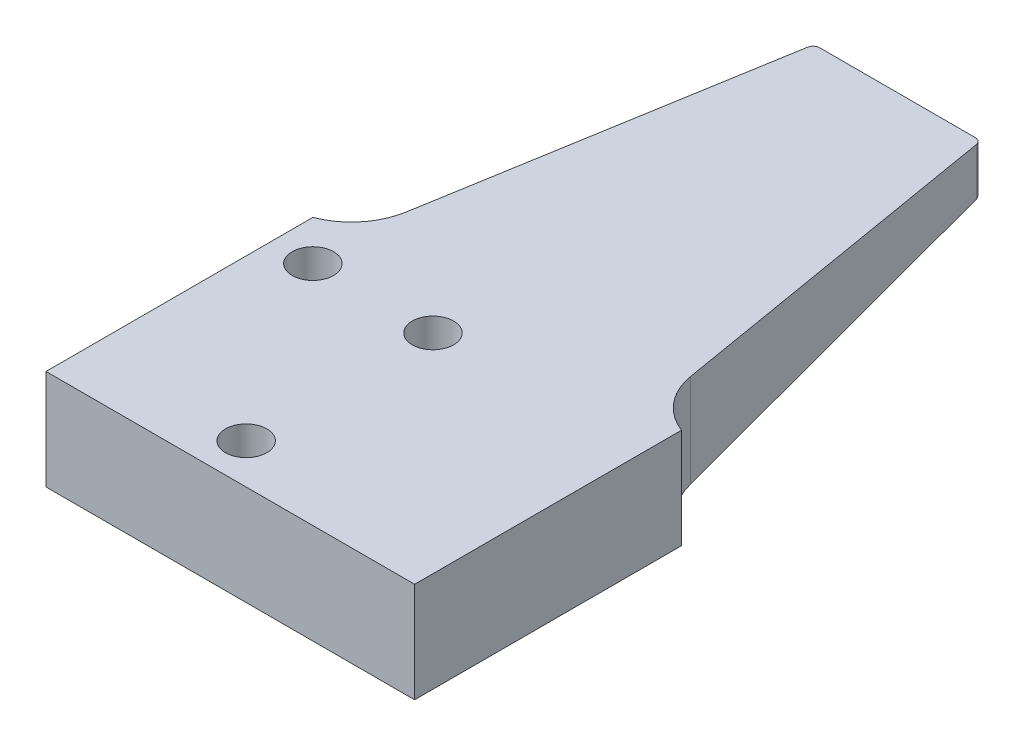
SolidWorks part; units mm, degrees
material "ABS"
ref_plane "Front Plane" through (0, 0, 0) normal (0, 0, 1) x (1, 0, 0)
ref_plane "Top Plane" through (0, 0, 0) normal (0, 1, 0) x (1, 0, 0)
ref_plane "Right Plane" through (0, 0, 0) normal (1, 0, 0) x (0, 0, -1)
sketch "Sketch1" plane through (0, 0, 0) normal (0, 1, 0) x (1, 0, 0)
  line L1 (0, 0) -> (55.25, 0)
  line L2 (0, 0) -> (0, 100)
  line L3 (0, 100) -> (55.25, 100)
  line L4 (55.25, 0) -> (55.25, 100)
  circle A6 centre (24, 6) radius 1.6
  circle A7 centre (6, 34) radius 1.6
  circle A8 centre (24, 34) radius 1.6
  dimension "D1" = 100
  dimension "D2" = 55.25
extrude "Boss-Extrude1" add sketch "Sketch1" along normal blind 15
sketch "Sketch2" plane through (0, 15, 0) normal (0, 1, 0) x (1, 0, 0)
  circle A0 centre (24, 34) radius 3.1
  circle A1 centre (24, 6) radius 3.1
  circle A4 centre (24, 34) radius 1.6 construction
  circle A5 centre (24, 6) radius 1.6 construction
  circle A6 centre (6, 34) radius 3.1
  circle A7 centre (6, 34) radius 1.6 construction
  dimension "D2" = 6.2
  dimension "D3" = 6.2
  dimension "D1" = 6.2
extrude "Cut-Extrude1" cut sketch "Sketch2" against normal blind 7.5
sketch "Sketch5" plane through (55.25, 0, 0) normal (1, 0, 0) x (0, 0, -1)
  line L0 (40, 0) -> (100, 8)
  line L1 (0, 0) -> (100, 0) construction
  line L2 (100, 8) -> (100, 0)
  line L3 (100, 0) -> (40, 0)
  dimension "D1" = 60
  dimension "D2" = 8
extrude "Cut-Extrude3" cut sketch "Sketch5" against normal up to next
sketch "Sketch3" plane through (0, 15, 0) normal (0, 1, 0) x (1, 0, 0)
  line L0 (0, 40) -> (55.25, 40) construction
  line L4 (55.25, 100) -> (0, 100) construction
  line L6 (40.125, 100) -> (55.25, 100)
  line L7 (55.25, 100) -> (55.25, 40)
  line L8 (15.125, 100) -> (0, 100)
  line L9 (0, 100) -> (0, 40)
  line L10 (15.125, 100) -> (5, 40)
  line L11 (40.125, 100) -> (50.25, 40)
  line L12 (50.25, 40) -> (55.25, 40)
  line L13 (5, 40) -> (0, 40)
  dimension "D1" = 25
  dimension "D2" = 60
  dimension "D3" = 5
extrude "Cut-Extrude2" cut sketch "Sketch3" against normal up to next
fillet "Fillet3" radius 10 2 edges at (5, 7.5, -40) (50.25, 7.5, -40)
fillet "Fillet4" radius 1 3 edges at (15.125, 11.5, -100) (27.625, 8, -100) (40.125, 11.5, -100)
equation "\"D3@Sketch2\"=\"D2@Sketch2\""
equation "\"D1@Sketch2\"=\"D2@Sketch2\""
